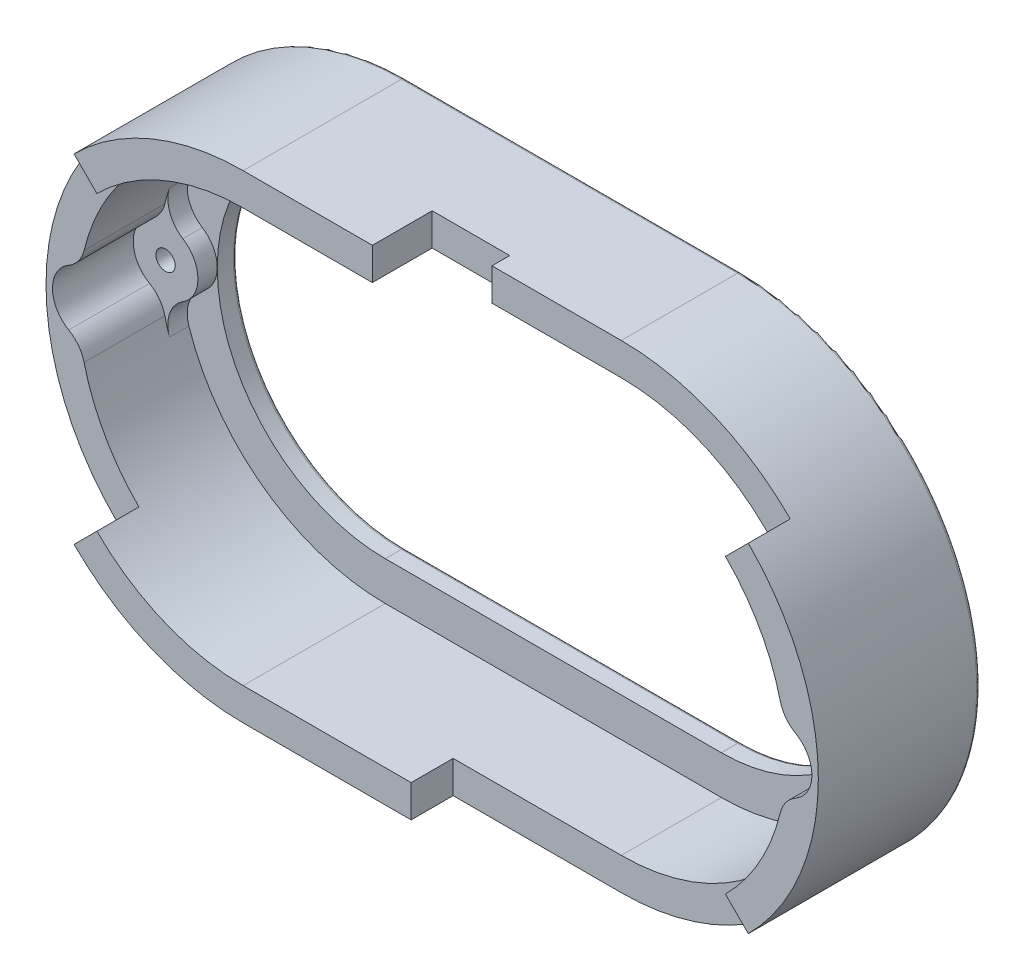
SolidWorks part; units mm, degrees
ref_plane "Front Plane" through (0, 0, 0) normal (0, 0, 1) x (1, 0, 0)
ref_plane "Top Plane" through (0, 0, 0) normal (0, 1, 0) x (1, 0, 0)
ref_plane "Right Plane" through (0, 0, 0) normal (1, 0, 0) x (0, 0, -1)
sketch "Sketch1" plane through (0, 0, 0) normal (0, 0, 1) x (1, 0, 0)
  line L0 (0, 0) -> (52, 0) construction
  line L1 (0, 37) -> (52, 37)
  line L2 (0, -37) -> (52, -37)
  line L3 (0, 0) -> (52, 0) construction
  line L4 (0, 26) -> (52, 26)
  line L5 (0, -26) -> (52, -26)
  line L6 (0, 32) -> (52, 32)
  line L7 (0, -32) -> (52, -32)
  line L8 (0, 26) -> (0, -26) construction
  line L9 (26, 0) -> (26, -26) construction
  line L11 (-36, 0) -> (-37, 0) construction
  arc A0 (0, 37) -> (0, -37) centre (0, 0) ccw
  arc A1 (52, -37) -> (52, 37) centre (52, 0) ccw
  arc A2 (0, 26) -> (0, -26) centre (0, 0) ccw
  arc A3 (52, -26) -> (52, 26) centre (52, 0) ccw
  arc A4 (52, -32) -> (52, 32) centre (52, 0) ccw
  arc A5 (0, 32) -> (0, -32) centre (0, 0) ccw
  circle A6 centre (-31, 0) radius 5
  circle A7 centre (83, 0) radius 5
  circle A8 centre (-31, 0) radius 1.5
  circle A10 centre (52, -31) radius 1.5
  circle A11 centre (52, -31) radius 5
  circle A12 centre (83, 0) radius 1.5
  circle A13 centre (21, 0) radius 5 [skipped]
  circle A14 centre (52, 31) radius 1.5
  circle A15 centre (52, 31) radius 5
  circle A16 centre (0, -31) radius 5
  circle A17 centre (0, 31) radius 5
  point P3 (26, 0)
  point P8 (26, 0)
  point P45 (52, 0)
  dimension "D5" = 52
  dimension "D2" = 1
  dimension "D4" = 3
  dimension "D1" = 6
  dimension "D3" = 11
  dimension "D6" = 4
  dimension "boxInteriorDiam" = 64
extrude "Boss-Extrude1" add sketch "Sketch1" along normal blind 25 contours L2 A1 L1 A0 A17 L6 A15 A4 A7 A11 L7 A16 A5 A6 | L6 A17 A5 | A5 A16 L7 | A15 L6 A14 A4 | A14 L6 A4 | A11 A4 A10 L7 | A10 A4 L7 region at (26, 35.5388, 0) region at (-0.0775, 33.6344, 0) region at (52.0794, 33.6728, 0) region at (52.0081, 32.2012, 0) region at (-0.0775, -33.6344, 0) region at (52.0794, -33.6728, 0) region at (52.0081, -32.2012, 0)
extrude "Boss-Extrude2" add sketch "Sketch1<3>" along normal blind 3 contours A17 L4 A15 L6 | A5 A17 L6 | A17 A5 A6 A2 | A8 A5 A6 | A16 A2 A6 A5 | A16 A5 L7 | A16 L7 A11 L5 | A10 L7 A4 | A11 L7 A10 A4 | A3 A11 A4 A7 | A7 A4 | A4 A15 A3 A7 | A15 A4 A14 L6 | A14 A4 L6 | A15 L6 A14 A4 | A14 L6 A4 | L2 A1 L1 A0 A17 L6 A15 A4 A7 A11 L7 A16 A5 A6 | L6 A17 A5 | A8 A5 A6 | A11 A4 A10 L7 | A10 A4 L7 | A7 A4 region at (26, 35.5388, 0) region at (26, 28.9238, 0) region at (0.0478, 29.3749, 0) region at (-19.1191, 19.1191, 0) region at (71.1191, 19.1191, 0) region at (51.9452, 29.1555, 0) region at (-29.115, 0, 0) region at (-19.1191, -19.1191, 0) region at (-0.0775, 33.6344, 0) region at (71.1191, -19.1191, 0) region at (81.115, 0, 0) region at (52.0794, 33.6728, 0) region at (26, -28.9238, 0) region at (0.0478, -29.3749, 0) region at (-33.6356, 0, 0) region at (51.9452, -29.1555, 0) region at (85.6356, 0, 0) region at (52.0081, 32.2012, 0) region at (51.999, 30.8506, 0) region at (52.0794, -33.6728, 0) region at (51.999, -30.8506, 0) region at (52.0081, -32.2012, 0)
sketch "Sketch1<3>" plane through (0, 0, 0) normal (0, 0, 1) x (1, 0, 0) same geometry as "Sketch1"
sketch "Sketch2" plane through (0, 37, 0) normal (0, 1, 0) x (1, 0, 0)
  line L0 (0, -25) -> (52, -25) construction
  line L1 (32, -34.25) -> (20, -34.25)
  line L2 (32, -34.25) -> (32, -15.75)
  line L3 (32, -15.75) -> (20, -15.75)
  line L4 (20, -34.25) -> (20, -15.75)
  line L5 (32, -34.25) -> (20, -15.75) construction
  line L6 (32, -15.75) -> (20, -34.25) construction
  point P0 (26, -25)
  dimension "D1" = 12
  dimension "D2" = 18.5
extrude "Cut-Extrude1" cut sketch "Sketch2" against normal up to surface (5 mm away) up to face at (26, 32, 14)
extrude "Boss-Extrude3" add sketch "Sketch1<4>" along normal blind 3 from surface contours A5 A8 | A8 A5 A6 | A7 A4 | A7 A4 region at (-29.115, 0, 0) region at (81.115, 0, 0) region at (-33.6356, 0, 0) region at (85.6356, 0, 0) starting at face at (-29.5, 0, 3)
sketch "Sketch1<4>" plane through (0, 0, 0) normal (0, 0, 1) x (1, 0, 0) same geometry as "Sketch1"
fillet "Fillet2" radius 5 4 edges at (83.6129, -4.9623, 4.5) (83.6129, 4.9623, 4.5) (-31.6129, -4.9623, 4.5) (-31.6129, 4.9623, 4.5)
fillet "Fillet3" radius 5 4 edges at (83.6129, -4.9623, 15.5) (83.6129, 4.9623, 15.5) (-31.6129, -4.9623, 15.5) (-31.6129, 4.9623, 15.5)
fillet "Fillet1" radius 0.5 10 edges at (26, -26, 0) (-26, 0, 0) (26, 26, 0) (78, 0, 0) (89, 0, 0) (26, 37, 0) (-37, 0, 0) (26, -37, 0) (-29.5, 0, 0) (84.5, 0, 0)
sketch "Sketch3" plane through (0, 0, 25) normal (0, 0, 1) x (1, 0, 0)
  line L0 (0, 0) -> (-38.2372, 38.2372)
  line L1 (0, 0) -> (52, 0)
  line L2 (26, -48.8901) -> (26, 48.8901)
  line L3 (52, 0) -> (90.2372, 38.2372)
  line L4 (52, 0) -> (90.2372, -38.2372)
  line L5 (0, 0) -> (-38.2372, -38.2372)
  line L6 (-38.2372, 38.2372) -> (-38.2372, -38.2372)
  line L7 (90.2372, 38.2372) -> (90.2372, -38.2372)
  line L8 (-38.2372, 38.2372) -> (26, 48.8901)
  line L9 (90.2372, 38.2372) -> (26, 48.8901)
  line L10 (-38.2372, -38.2372) -> (26, -48.8901)
  line L11 (90.2372, -38.2372) -> (26, -48.8901)
  arc A0 (52, -37) -> (52, 37) centre (52, 0) ccw construction
  point P13 (26, 0)
  arc M9 (83.1072, -7.506) -> (52, -32) centre (52, 0) cw
  line M13 (52, -32) -> (0, -32)
  arc M17 (0, -32) -> (-31.1072, -7.506) centre (0, 0) cw
  arc M18 (-31.1072, -7.506) -> (-33.4839, -4.3394) centre (-35.9677, -8.6788) ccw
  arc M19 (-33.4839, -4.3394) -> (-33.4839, 4.3394) centre (-31, 0) cw
  arc M20 (-33.4839, 4.3394) -> (-31.1072, 7.506) centre (-35.9677, 8.6788) ccw
  arc M21 (-31.1072, 7.506) -> (0, 32) centre (0, 0) cw
  arc M28 (0, 37) -> (0, -37) centre (0, 0) ccw
  line M29 (0, -37) -> (52, -37)
  arc M30 (52, -37) -> (52, 37) centre (52, 0) ccw
  line M31 (52, 37) -> (32, 37)
  line M32 (32, 37) -> (32, 32)
  line M33 (32, 32) -> (52, 32)
  arc M37 (52, 32) -> (83.1072, 7.506) centre (52, 0) cw
  dimension "D1" = 135
extrude "Cut-Extrude4" cut sketch "Sketch3" against normal blind 6.5 contours L5 L0 M17 M18 M19 M20 M21 M28 | L3 M37 M30 M31 M32 M33 | L4 L2 M9 M13 M29 M30 region at (-28.3842, 15.9173, 25) region at (52.2114, -32.7727, 25) region at (55.1685, 32.5526, 25)
equation "\"speakerCenterDist\" = 40"
equation "\"speakerDiam\" = 50"
equation "\"boxInteriorDiam\" = 64"
